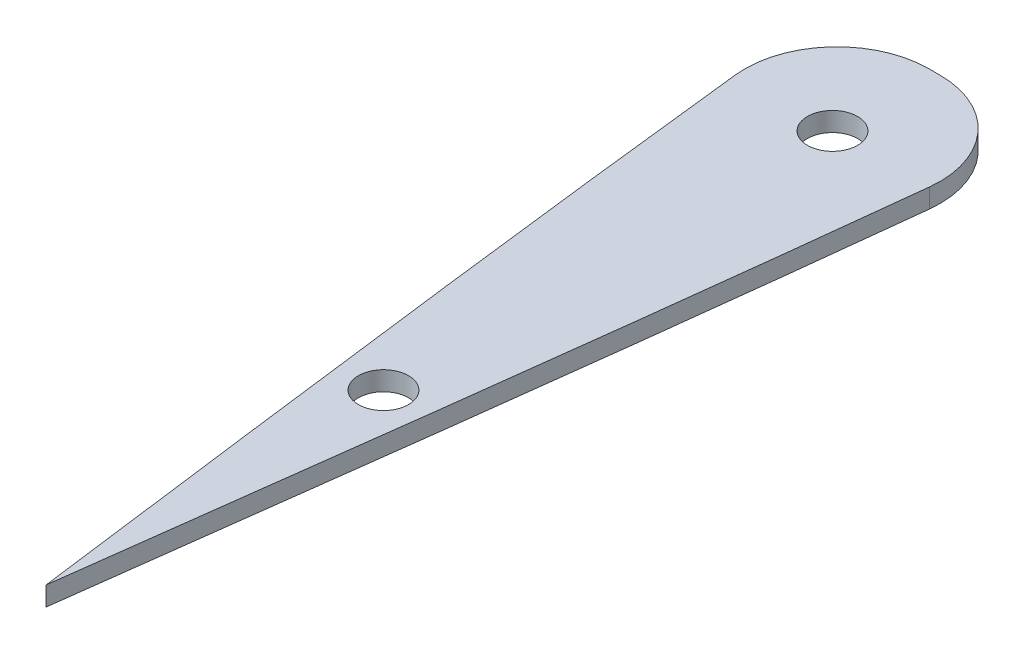
SolidWorks part; units mm, degrees
material "Balsa"
ref_plane "Front Plane" through (0, 0, 0) normal (0, 0, 1) x (1, 0, 0)
ref_plane "Top Plane" through (0, 0, 0) normal (0, 1, 0) x (1, 0, 0)
ref_plane "Right Plane" through (0, 0, 0) normal (1, 0, 0) x (0, 0, -1)
sketch "Sketch1" plane through (0, 0, 0) normal (0, 1, 0) x (1, 0, 0)
  line L0 (1.1081, 1.7265) -> (-45.0799, 1.7265) construction
  line L1 (-45.0799, 1.7265) -> (-45.0799, -11.2275) construction
  line L2 (-45.0799, -11.2275) -> (43.7517, -11.2275) construction
  line L3 (1.1081, 103.3269) -> (1.1081, -99.8738) construction
  line L4 (-45.0799, -11.2275) -> (-45.0799, -20.7525) construction
  line L5 (-28.2049, 1.7265) -> (-28.2049, -3.6075) construction
  line L6 (-9.9553, -3.6075) -> (-6.7697, -3.6075)
  line L7 (-28.2049, -3.6075) -> (-9.9553, -3.6075) construction
  line L8 (-6.7697, -3.6075) -> (1.1081, -3.6075) construction
  line L9 (8.9859, -3.6075) -> (12.1715, -3.6075)
  line L10 (12.1715, -3.6075) -> (18.1346, -3.6075) construction
  line L11 (12.1715, -3.6075) -> (18.1346, -3.6075) construction
  line L12 (18.1346, -3.6075) -> (29.3788, -3.6075) construction
  line L13 (1.1081, -3.6075) -> (8.9859, -3.6075) construction
  line L14 (-6.7697, -3.6075) -> (8.9859, -3.6075)
  circle A0 centre (1.1081, -11.3265) radius 1.9844 construction
  circle A1 centre (1.1081, -11.3265) radius 1.9844
  spline S0 degree 3 poles (1.1081, -99.8738) (4.5273, -73.5318) (7.9866, -47.1872) (10.6029, -20.7525) knots 0 0 0 0 0.38497 0.38497 0.38497 0.38497
  spline S3 degree 3 poles (1.1081, -99.8738) (-2.3112, -73.5318) (-5.7704, -47.1872) (-8.3867, -20.7525) knots 0 0 0 0 0.38497 0.38497 0.38497 0.38497
  spline S4 degree 3 poles (10.6029, -20.7525) (11.1, -15.7302) (11.6306, -10.016) (12.114, -4.2968) (12.1715, -3.6075) knots 0.38497 0.38497 0.38497 0.38497 0.458109 0.468132 0.468132 0.468132 0.468132
  spline S5 degree 3 poles (-8.3867, -20.7525) (-8.8838, -15.7302) (-9.4144, -10.016) (-9.8978, -4.2968) (-9.9553, -3.6075) knots 0.38497 0.38497 0.38497 0.38497 0.458109 0.468132 0.468132 0.468132 0.468132
  spline S8 degree 3 poles (12.1715, -3.6075) (12.8364, 4.367) (14.1908, 23.6726) (14.0058, 48.0803) (13.0188, 67.5796) (11.3266, 78.9472) (9.5869, 86.9693) (8.1237, 93.6397) (6.4505, 97.563) (4.8164, 101.3994) (2.3437, 102.5279) (1.1081, 103.3269) knots 0.468132 0.468132 0.468132 0.468132 0.584075 0.748482 0.821537 0.866809 0.914778 0.94069 0.965303 0.976863 1 1 1 1 construction
  spline S9 degree 3 poles (1.1081, 99.6196) (1.2739, 99.518) (1.6209, 99.2976) (2.0134, 99.0137) (2.3095, 98.7539) (2.4667, 98.5788) (2.6076, 98.3713) (2.8163, 97.9774) (3.0534, 97.4394) (3.4327, 96.5453) (3.8774, 95.496) (4.541, 93.8448) (5.2023, 91.9048) (5.8236, 89.3366) (6.4213, 86.5662) (7.0145, 83.8293) (7.767, 80.1951) (8.6007, 75.6781) (9.6391, 68.4081) (10.3034, 59.2354) (10.6788, 47.9926) (10.8555, 36.7918) (10.7415, 25.5951) (10.3009, 14.4244) (9.6564, 4.6878) (9.1767, -1.3266) (8.9859, -3.6075) knots 0.118744 0.118744 0.118744 0.118744 0.122149 0.125554 0.12896 0.132365 0.13577 0.139175 0.142581 0.145986 0.152796 0.159607 0.173228 0.186849 0.20047 0.214091 0.227711 0.254953 0.282195 0.336679 0.391163 0.445646 0.50013 0.554614 0.609098 0.642376 0.642376 0.642376 0.642376 construction
  spline S10 degree 3 poles (-7.1984, 1.7265) (-7.237, 2.2289) (-7.5577, 6.4638) (-8.0847, 14.4244) (-8.5253, 25.5951) (-8.6393, 36.7918) (-8.4626, 47.9926) (-8.0872, 59.2354) (-7.4229, 68.4081) (-6.3845, 75.6781) (-5.5508, 80.1951) (-4.7983, 83.8293) (-4.2051, 86.5662) (-3.6074, 89.3366) (-2.9861, 91.9048) (-2.3248, 93.8448) (-1.6612, 95.496) (-1.2165, 96.5453) (-0.8372, 97.4394) (-0.6001, 97.9774) (-0.3914, 98.3713) (-0.2505, 98.5788) (-0.0933, 98.7539) (0.2028, 99.0137) (0.5953, 99.2976) (0.9423, 99.518) (1.1081, 99.6196) knots 0.492798 0.492798 0.492798 0.492798 0.50013 0.554614 0.609098 0.663581 0.718065 0.772549 0.827033 0.854275 0.881516 0.895137 0.908758 0.922379 0.936 0.949621 0.956432 0.963242 0.966647 0.970053 0.973458 0.976863 0.980268 0.983674 0.987079 0.990484 0.990484 0.990484 0.990484 construction
  spline S11 degree 3 poles (-10.3826, 1.7265) (-10.8572, 7.9268) (-11.9611, 25.4575) (-11.7896, 48.0803) (-10.8026, 67.5796) (-9.1104, 78.9472) (-7.3707, 86.9693) (-5.9075, 93.6397) (-4.2343, 97.563) (-2.6002, 101.3994) (-0.1276, 102.5279) (1.1081, 103.3269) knots 0.493976 0.493976 0.493976 0.493976 0.584075 0.748482 0.821537 0.866809 0.914778 0.94069 0.965303 0.976863 1 1 1 1 construction
  spline S12 degree 3 poles (-9.9553, -3.6075) (-10.1035, -1.8299) (-10.2465, -0.0519) (-10.3826, 1.7265) knots 0.468132 0.468132 0.468132 0.468132 0.493976 0.493976 0.493976 0.493976 construction
  spline S13 degree 3 poles (-6.7697, -3.6075) (-6.9185, -1.8292) (-7.0618, -0.0511) (-7.1984, 1.7265) knots 0.466852 0.466852 0.466852 0.466852 0.492798 0.492798 0.492798 0.492798 construction
  dimension "D4" = 3.9688
  dimension "D1" = 12.954
  dimension "D2" = 9.525
  dimension "D3" = 5.334
extrude "Boss-Extrude1" add sketch "Sketch1" along normal blind 169.8727
sketch "Sketch2" plane through (0, 169.8727, 0) normal (0, 1, 0) x (1, 0, 0)
  line L1 (-9.9553, -3.6075) -> (25.8085, -3.6075)
  line L2 (-9.9553, -3.6075) -> (-9.9553, -26.3125)
  line L3 (-9.9553, -26.3125) -> (25.8085, -26.3125)
  line L4 (25.8085, -3.6075) -> (25.8085, -26.3125)
  circle A0 centre (1.1081, -11.3265) radius 1.9844 construction
  dimension "D1" = 14.986
extrude "Cut-Extrude1" cut sketch "Sketch2" against normal blind 23.0581
extrude "Cut-Extrude2" cut sketch "Sketch2<2>" along normal blind 23.0581 from surface starting at face at (-1.1046, 0, 29.7187)
sketch "Sketch2<2>" plane through (0, 169.8727, 0) normal (0, 1, 0) x (1, 0, 0) same geometry as "Sketch2"
fillet "Fillet1" radius 7.62 6 edges at (-7.8242, 11.5291, 26.3125) (10.0403, 11.5291, 26.3125) (12.1715, 84.9363, 3.6075) (-7.8242, 158.3436, 26.3125) (10.0403, 158.3436, 26.3125)
sketch "Sketch6" plane through (0, 0, 0) normal (0, -1, 0) x (1, 0, 0)
  line L0 (1.1081, 3.6075) -> (1.1081, 99.8738) construction
  line L1 (-1.6395, 3.6075) -> (3.8557, 3.6075) construction
  line L2 (-6.9254, 34.7606) -> (9.1416, 34.7606) construction
  circle A0 centre (1.1081, 71.9338) radius 2.075
  circle A1 centre (1.1081, 34.7606) radius 2.075
  dimension "D1" = 4.15
  dimension "D2" = 27.94
extrude "Cut-Extrude3" cut sketch "Sketch6" against normal through all both and the other way through all
sketch "Sketch7" plane through (0, 0, 0) normal (1, 0, 0) x (0, 0, -1)
  line L0 (-3.6075, 146.8145) -> (-3.6075, 23.0581) construction
  line L1 (-99.8738, 0) -> (-3.6075, 0)
  line L2 (-99.8738, 0) -> (-99.8738, 159.2848)
  line L3 (-99.8738, 159.2848) -> (-3.6075, 159.2848)
  line L4 (-3.6075, 0) -> (-3.6075, 159.2848)
  line L6 (-99.8738, 169.8727) -> (-3.6075, 169.8727)
  line L7 (-99.8738, 169.8727) -> (-99.8738, 160.8723)
  line L8 (-99.8738, 160.8723) -> (-3.6075, 160.8723)
  line L9 (-3.6075, 169.8727) -> (-3.6075, 160.8723)
  dimension "D2" = 1.5875
extrude "Cut-Extrude4" cut sketch "Sketch7" against normal through all both and the other way through all
